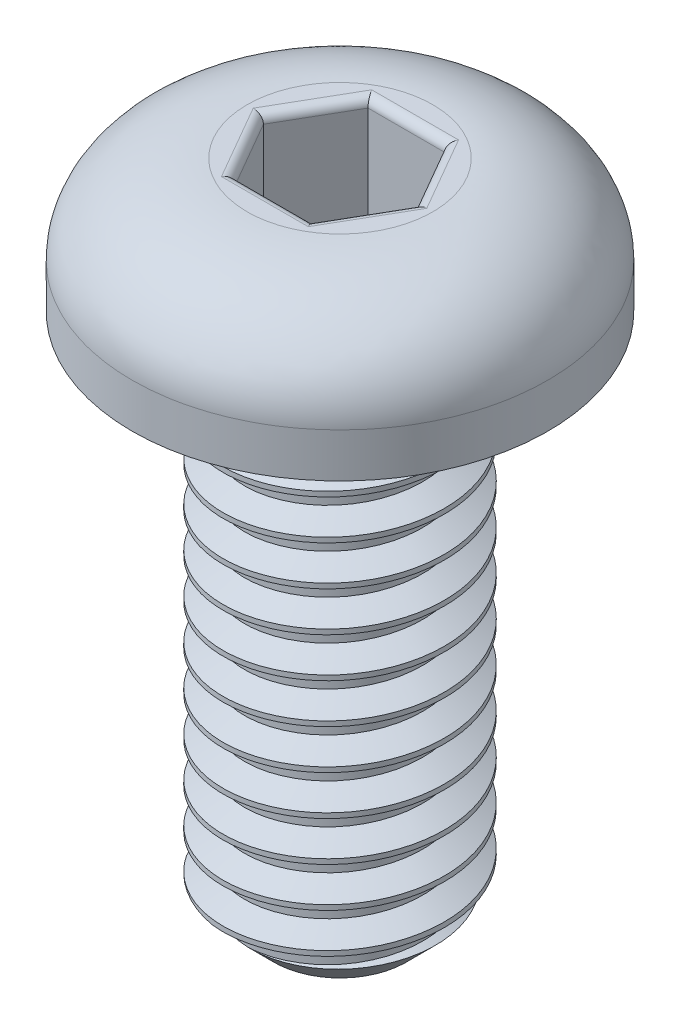
SolidWorks part; units mm, degrees
material "AISI 304"
ref_plane "Plano frontal" through (0, 0, 0) normal (0, 0, 1) x (1, 0, 0)
ref_plane "Plano superior" through (0, 0, 0) normal (0, 1, 0) x (1, 0, 0)
ref_plane "Plano direito" through (0, 0, 0) normal (1, 0, 0) x (0, 0, -1)
sketch "Esboço1" plane through (0, 0, 0) normal (0, 1, 0) x (1, 0, 0)
  circle A0 centre (0, 0) radius 2.35
  dimension "D1" = 4.7
extrude "Ressalto-extrusão1" add sketch "Esboço1" along normal blind 1.5 contours A0
sketch "Esboço3" plane through (0, 1.5, 0) normal (0, 1, 0) x (1, 0, 0)
  line L1 (0.866, 0) -> (0.433, 0.75)
  line L2 (0.433, 0.75) -> (-0.433, 0.75)
  line L3 (-0.433, 0.75) -> (-0.866, 0)
  line L4 (-0.866, 0) -> (-0.433, -0.75)
  line L5 (-0.433, -0.75) -> (0.433, -0.75)
  line L6 (0.433, -0.75) -> (0.866, 0)
  circle A0 centre (0, 0) radius 0.75 construction
  dimension "D1" = 1.5
extrude "Corte-extrusão1" cut sketch "Esboço3" against normal blind 1.45
chamfer "Chanfro3" distance 0.15 angle 70 6 edges at (0, 0.05, 0.75) (-0.6495, 0.05, 0.375) (-0.6495, 0.05, -0.375) (0, 0.05, -0.75) (0.6495, 0.05, -0.375) (0.6495, 0.05, 0.375) first distance on face at (0, 0.775, 0.75) first distance on face at (-0.6495, 0.775, 0.375) first distance on face at (-0.6495, 0.775, -0.375) first distance on face at (0, 0.775, -0.75) first distance on face at (0.6495, 0.775, -0.375) first distance on face at (0.6495, 0.775, 0.375)
sketch "Esboço4" plane through (0, 0, 0) normal (0, -1, 0) x (1, 0, 0)
  circle A0 centre (0, 0) radius 1.25
  dimension "D1" = 2.5
extrude "Ressalto-extrusão2" add sketch "Esboço4" along normal blind 6
chamfer "Chanfro4" distance 0.5 angle 45 1 edges at (0, -6, -1.25)
fillet "Filete2" radius 0.2 1 edges at (0, 0, -1.25)
thread "Rosca1" pitch 0.45 method cut profile "Perfil da rosca1" start angle 0, offset 0, length 0, pitch 0.45, diameter 2.5
ref_plane "Plano1" through (-1.25, -0.2, 0) normal (0, 0, 1) x (-1, 0, 0)
sketch "Perfil da rosca1" plane through (-1.25, -0.2, 0) normal (0, 0, 1) x (-1, 0, 0)
  line L0 (0, 0) -> (0, 0.45) construction
  line L11 (0, 0) -> (0, 0.3937)
  line L12 (0, 0.3937) -> (-0.2436, 0.2531)
  line L13 (-0.2436, 0.2531) -> (-0.2436, 0.1406)
  line L15 (-0.2436, 0.1406) -> (0, 0)
  line L17 (-0.2436, 0.1969) -> (0, 0.1969) construction
  point P2 (0, 0)
  dimension "Pitch" = 0.45
  dimension "Profile_Angle" = 60
  dimension "Profile_Land" = 0.1125
  dimension "Profile_Height" = 0.2436
fillet "Filete6" radius 1 1 edges at (0, 1.5, 2.35) second distance 1.3 first distance on face at (0, 1.5, 2.35)
fillet "Filete7" radius 0.1 6 edges at (-0.6495, 1.5, -0.375) (-0.6495, 1.5, 0.375) (0, 1.5, 0.75) (0.6495, 1.5, 0.375) (0.6495, 1.5, -0.375) (0, 1.5, -0.75)
